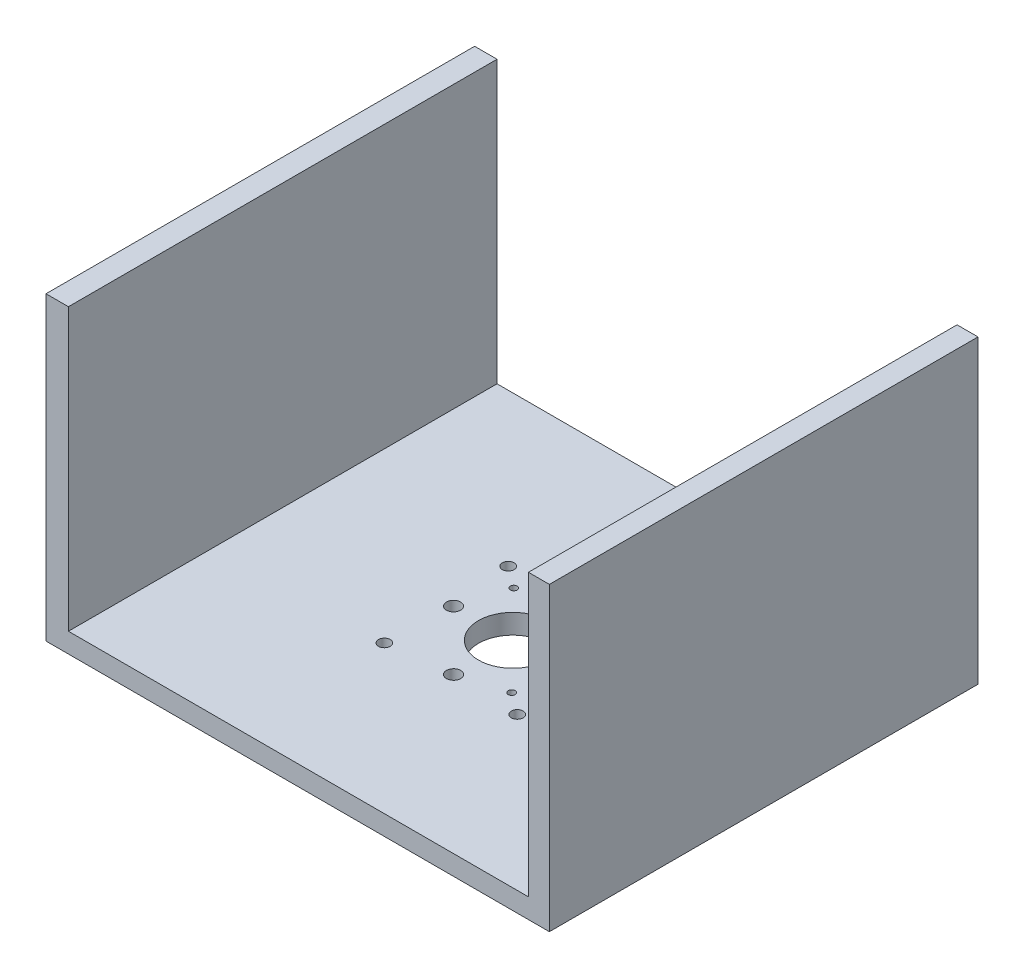
SolidWorks part; units mm, degrees
ref_plane "Front Plane" through (0, 0, 0) normal (0, 0, 1) x (1, 0, 0)
ref_plane "Top Plane" through (0, 0, 0) normal (0, 1, 0) x (1, 0, 0)
ref_plane "Right Plane" through (0, 0, 0) normal (1, 0, 0) x (0, 0, -1)
sketch "Sketch1" plane through (0, 0, 0) normal (0, 1, 0) x (1, 0, 0)
  line L1 (-58.2596, -54.2873) -> (58.2596, -54.2873)
  line L2 (-58.2596, -54.2873) -> (-58.2596, 54.2873)
  line L3 (-58.2596, 54.2873) -> (58.2596, 54.2873)
  line L4 (58.2596, -54.2873) -> (58.2596, 54.2873)
  line L5 (-58.2596, -54.2873) -> (58.2596, 54.2873) construction
  line L6 (-58.2596, 54.2873) -> (58.2596, -54.2873) construction
  line L7 (-58.2596, 54.2873) -> (-63.9431, 54.2873)
  line L8 (-58.2596, 54.2873) -> (-58.2596, -54.2873)
  line L9 (-58.2596, -54.2873) -> (-63.9431, -54.2873)
  line L10 (-63.9431, 54.2873) -> (-63.9431, -54.2873)
  line L11 (58.2596, 54.2873) -> (63.5668, 54.2873)
  line L12 (58.2596, 54.2873) -> (58.2596, -54.2873)
  line L13 (58.2596, -54.2873) -> (63.5668, -54.2873)
  line L14 (63.5668, 54.2873) -> (63.5668, -54.2873)
  circle A0 centre (0, 0) radius 15 construction
  circle A1 centre (0, 15) radius 1.8
  circle A2 centre (15, 0) radius 1.8
  circle A3 centre (0, -15) radius 1.8
  circle A4 centre (-15, 0) radius 1.8
  circle A5 centre (0, 0) radius 23.01 construction
  circle A6 centre (-16.8343, 15.6865) radius 1.5
  circle A7 centre (15.6865, 16.8343) radius 1.5
  circle A8 centre (16.8343, -15.6865) radius 1.5
  circle A9 centre (-15.6865, -16.8343) radius 1.5
  circle A10 centre (0, 0) radius 16.22 construction
  circle A11 centre (-11.3281, 11.6087) radius 0.875
  circle A12 centre (11.3281, -11.6087) radius 0.875
  circle A13 centre (0, 0) radius 8.6768
  point P0 (0, 0)
  point P19 (0, 0)
  point P29 (0, 0)
  point P34 (0, 0)
  dimension "D1" = 4
  dimension "D2" = 4
  dimension "D3" = 2
extrude "Boss-Extrude2" add sketch "Sketch1" along normal blind 76.2 contours L7 L10 L9 L2 | L14 L11 L4 L13 region at (-61.1014, 0, 0) region at (60.9132, 0, 0)
extrude "Boss-Extrude3" add sketch "Sketch1<5>" along normal blind 5 contours L1 L4 L3 L2 A12 A11 A9 A8 A7 A6 A4 A3 A2 A1 region at (-56.6669, 0, 0)
sketch "Sketch1<5>" plane through (0, 0, 0) normal (0, 1, 0) x (1, 0, 0) same geometry as "Sketch1"
